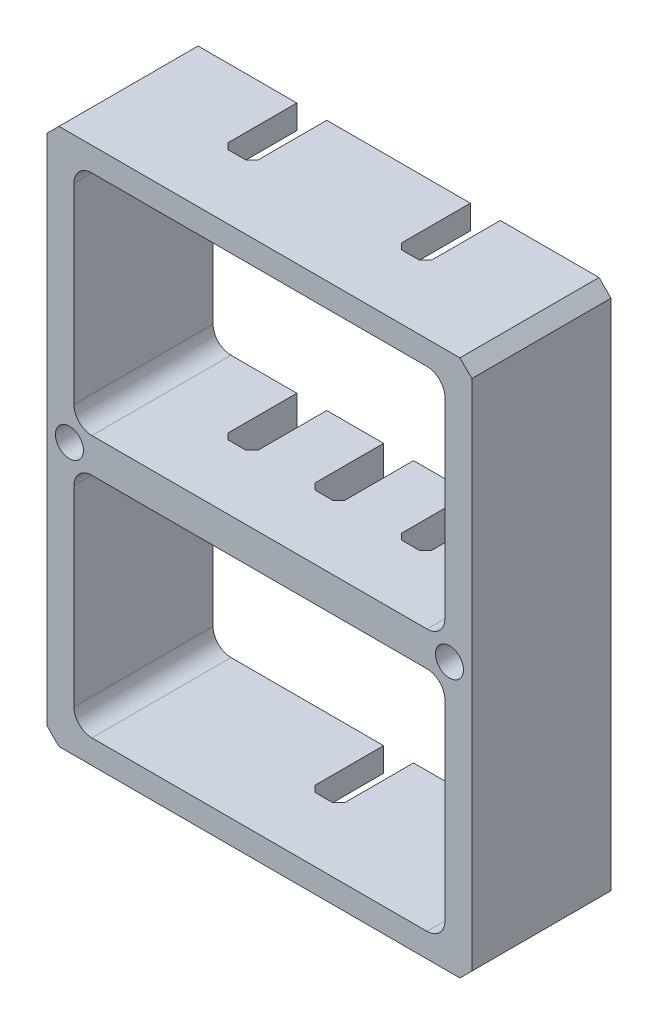
SolidWorks part; units mm, degrees
ref_plane "Front Plane" through (0, 0, 0) normal (0, 0, 1) x (1, 0, 0)
ref_plane "Top Plane" through (0, 0, 0) normal (0, 1, 0) x (1, 0, 0)
ref_plane "Right Plane" through (0, 0, 0) normal (1, 0, 0) x (0, 0, -1)
sketch "Sketch1" plane through (0, 0, 0) normal (0, 0, 1) x (1, 0, 0)
  line L4 (30.226, -70.2945) -> (30.226, -77.9145) construction
  line L5 (15.494, -69.7865) -> (30.226, -69.7865) construction
  line L6 (15.494, -69.7865) -> (15.494, -78.4225) construction
  line L7 (15.494, -78.4225) -> (30.226, -78.4225) construction
  line L8 (10.033, -79.9465) -> (31.877, -79.9465)
  line L9 (31.877, -79.9465) -> (31.877, -64.0516)
  line L10 (35.687, -57.15) -> (13.843, -57.15)
  line L11 (13.843, -57.15) -> (13.843, -73.0449)
  line L12 (13.843, -79.9465) -> (31.877, -79.9465)
  line L13 (31.877, -79.9465) -> (31.877, -57.15)
  line L14 (31.877, -57.15) -> (13.843, -57.15)
  line L15 (13.843, -57.15) -> (13.843, -79.9465)
  line L16 (30.226, -69.7865) -> (30.226, -78.4225) construction
  line L17 (22.86, -78.4225) -> (22.86, -69.7865) construction
  line L18 (15.494, -74.1045) -> (30.226, -74.1045) construction
  line L19 (16.002, -69.7865) -> (29.718, -69.7865) construction
  line L20 (15.494, -77.9145) -> (15.494, -70.2945) construction
  line L21 (29.718, -78.4225) -> (16.002, -78.4225) construction
  line L22 (14.986, -69.2785) -> (30.734, -69.2785)
  line L23 (30.734, -69.2785) -> (30.734, -78.9305)
  line L24 (14.986, -78.9305) -> (30.734, -78.9305)
  line L25 (14.986, -69.2785) -> (14.986, -78.9305)
  line L26 (13.843, -68.5482) -> (31.877, -68.5482) construction
  line L27 (14.986, -67.818) -> (14.986, -58.166)
  line L28 (14.986, -58.166) -> (30.734, -58.166)
  line L29 (30.734, -67.818) -> (30.734, -58.166)
  line L30 (14.986, -67.818) -> (30.734, -67.818)
  line L51 (31.877, -64.0516) -> (35.687, -60.2416)
  line L53 (35.687, -60.2416) -> (35.687, -57.15)
  line L55 (13.843, -73.0449) -> (10.033, -76.8549)
  line L57 (10.033, -76.8549) -> (10.033, -79.9465)
  point P208 (22.86, -74.1045)
  dimension "D2" = 0.508
  dimension "D1" = 0.508
extrude "Boss-Extrude1" add sketch "Sketch1" along normal offset from surface (5.9055 mm away) 1.5875 contours L14 L15 L12 L13 L30 L27 L28 L29 L25 L22 L23 L24 region at (22.86, -68.5482, 0)
sketch "Sketch2" plane through (0, 0, 0) normal (0, 0, -1) x (-1, 0, 0)
  line L0 (-18.796, -57.404) -> (-19.558, -57.404) construction
  line L3 (-26.162, -57.404) -> (-26.924, -57.404) construction
  line L5 (-23.241, -68.58) -> (-22.479, -68.58) construction
  line L8 (-18.796, -68.5165) -> (-19.558, -68.5165) construction
  line L9 (-26.162, -68.5165) -> (-26.924, -68.5165) construction
  line L10 (-23.241, -79.6925) -> (-22.479, -79.6925) construction
  line L11 (-22.86, -78.9305) -> (-22.86, -79.9465)
  line L12 (-30.734, -78.9305) -> (-14.986, -78.9305) construction
  line L13 (-31.877, -79.9465) -> (-13.843, -79.9465) construction
  line L14 (-19.177, -57.15) -> (-19.177, -58.166)
  line L15 (-13.843, -57.15) -> (-31.877, -57.15) construction
  line L16 (-30.734, -58.166) -> (-14.986, -58.166) construction
  line L17 (-26.543, -57.15) -> (-26.543, -58.166)
  line L18 (-22.86, -69.2785) -> (-22.86, -67.818)
  line L19 (-30.734, -69.2785) -> (-14.986, -69.2785) construction
  line L20 (-30.734, -67.818) -> (-14.986, -67.818) construction
  line L21 (-19.177, -69.2785) -> (-19.177, -67.818)
  line L22 (-26.543, -69.2785) -> (-26.543, -67.818)
  point P0 (-19.177, -57.404)
  point P1 (-26.543, -57.404)
  point P4 (-22.86, -68.58)
  point P7 (-19.177, -68.5165)
  point P10 (-26.543, -68.5165)
  point P13 (-22.86, -79.6925)
extrude "Cut-Extrude-Thin2" cut sketch "Sketch2" against normal blind 3.175 thin contours L14 | L17 | L21 | L18 | L22 | L11 thin type mid plane wall 1.27
chamfer "Chamfer1" distance 0.254 angle 45 12 edges at (23.495, -79.4385, 3.175) (22.225, -79.4385, 3.175) (27.178, -68.5482, 3.175) (25.908, -68.5482, 3.175) (22.225, -68.5482, 3.175) (23.495, -68.5482, 3.175) (19.812, -68.5482, 3.175) (18.542, -68.5482, 3.175) (18.542, -57.658, 3.175) (19.812, -57.658, 3.175) (25.908, -57.658, 3.175) (27.178, -57.658, 3.175)
chamfer "Chamfer2" distance 0.508 angle 45 4 edges at (31.877, -57.15, 2.9527) (13.843, -57.15, 2.9528) (13.843, -79.9465, 2.9528) (31.877, -79.9465, 2.9528)
fillet "Fillet1" radius 0.762 8 edges at (14.986, -78.9305, 2.9528) (30.734, -78.9305, 2.9528) (30.734, -69.2785, 2.9528) (14.986, -69.2785, 2.9528) (14.986, -67.818, 2.9528) (30.734, -67.818, 2.9528) (14.986, -58.166, 2.9528) (30.734, -58.166, 2.9528)
hole_wizard "#0-80 Tapped Hole1" positions "Sketch4" profile "Sketch3" tap size "#0-80" standard "ANSI Inch" end condition through all
sketch "Sketch4" plane through (0, 0, 0) normal (0, 0, -1) x (-1, 0, 0)
  line L0 (-15.748, -69.2785) -> (-15.748, -67.818) construction
  line L2 (-15.748, -68.5482) -> (-13.843, -68.5482) construction
  line L3 (-13.843, -57.658) -> (-13.843, -79.4385) construction
  line L5 (-22.86, -57.15) -> (-22.86, -79.9465) construction
  line L6 (-25.908, -57.15) -> (-19.812, -57.15) construction
  line L7 (-22.479, -79.9465) -> (-23.241, -79.9465) construction
  point P12 (-14.7955, -68.5482)
  point P25 (-30.9245, -68.5482)
sketch "Sketch3" plane through (14.7955, -68.5482, 0) normal (1, 0, 0) x (0, 1, 0)
  line L0 (0, 0) -> (0, 5.9055)
  line L1 (0, 5.9055) -> (0.5956, 5.9055)
  line L2 (0.5956, 5.9055) -> (0.5956, 0)
  line L5 (0.5956, 0) -> (0, 0)
  line L11 (0, -6.35) -> (0, 107.95) construction
  dimension "Thru Tap Drill Dia." = 1.1913
  dimension "Thru Tap Drill Depth" = 5.9055
cosmetic thread "Hole Thread1" parameters "D2"=1.524
cosmetic thread "Hole Thread2" parameters "D2"=1.524
